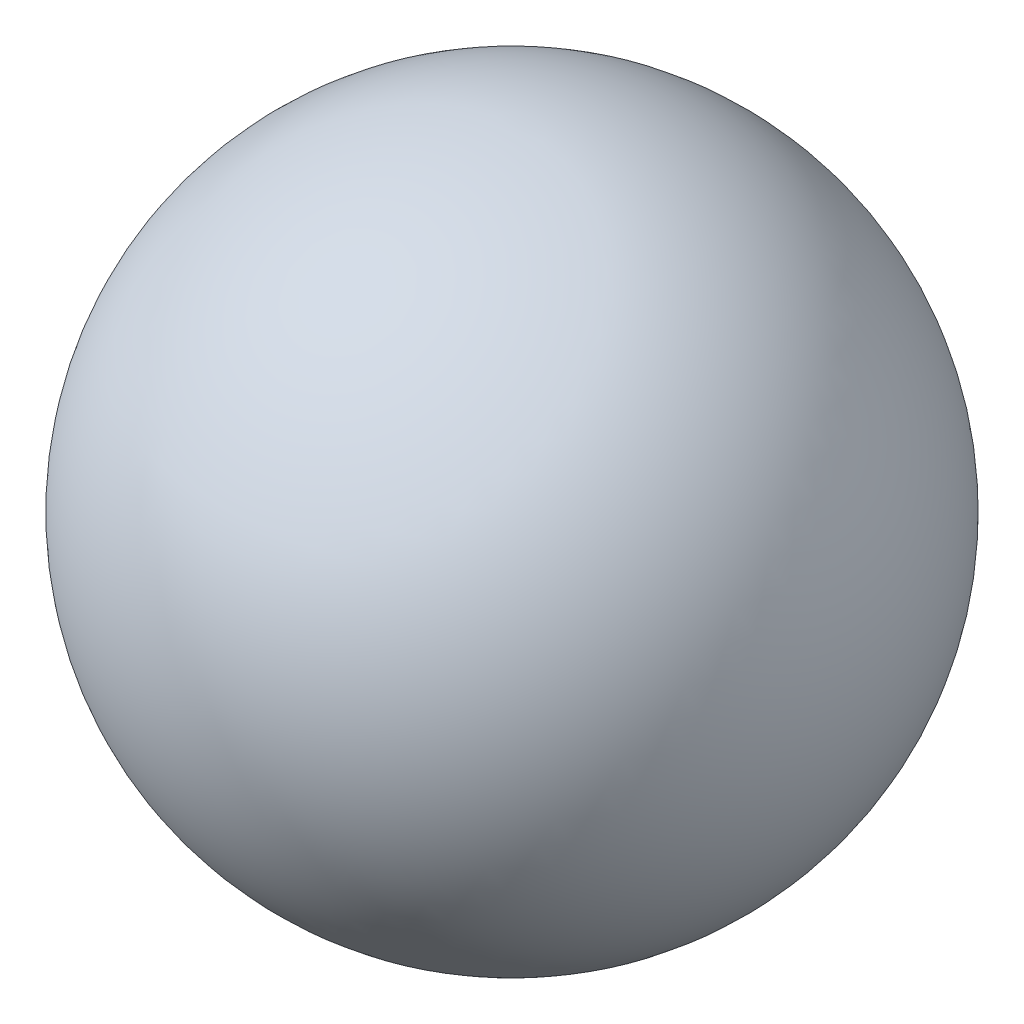
SolidWorks part; units mm, degrees
material "Aço cromo inoxidável"
ref_plane "Plano frontal" through (0, 0, 0) normal (0, 0, 1) x (1, 0, 0)
ref_plane "Plano superior" through (0, 0, 0) normal (0, 1, 0) x (1, 0, 0)
ref_plane "Plano direito" through (0, 0, 0) normal (1, 0, 0) x (0, 0, -1)
sketch "Esboço1" plane through (0, 0, 0) normal (0, 0, 1) x (1, 0, 0)
  line L0 (0, 2.75) -> (0, -2.75)
  line L1 (0, -2.75) -> (0, 2.75) construction
  arc A0 (0, 2.75) -> (0, -2.75) centre (0, 0) ccw
  dimension "D1" = 5.5
revolve "Revolução1" add sketch "Esboço1" angle 360 about L1
ref_axis "Eixo1" through (0, -3.025, 0) along (0, 1, 0)
